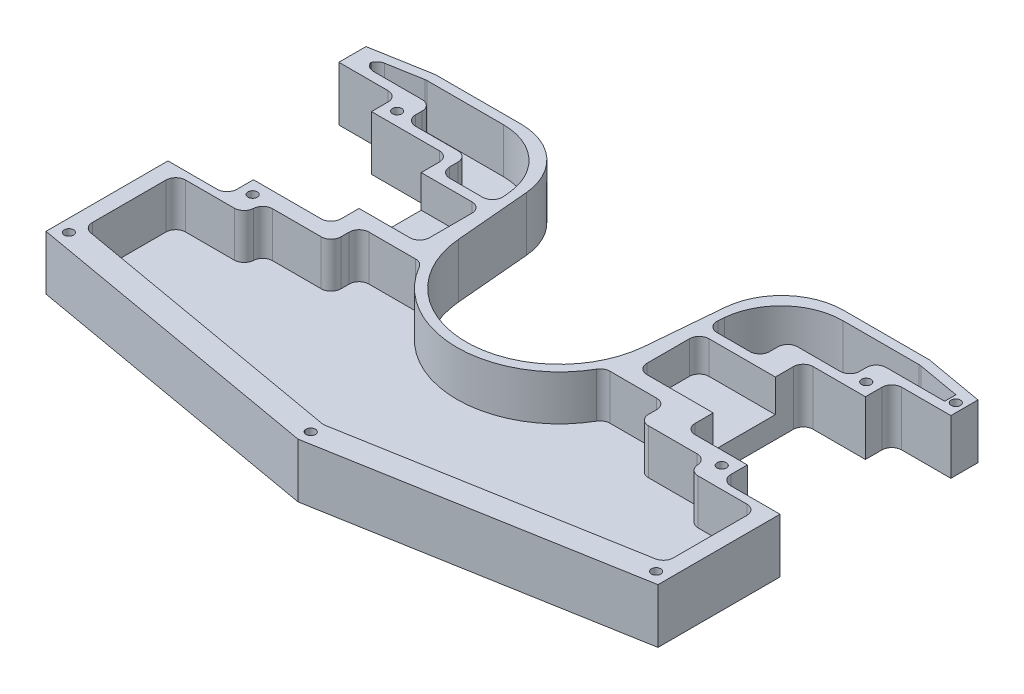
SolidWorks part; units mm, degrees
material "Nailon 101"
ref_plane "Alzado" through (0, 0, 0) normal (0, 0, 1) x (1, 0, 0)
ref_plane "Planta" through (0, 0, 0) normal (0, 1, 0) x (1, 0, 0)
ref_plane "Vista lateral" through (0, 0, 0) normal (1, 0, 0) x (0, 0, -1)
sketch "Croquis2" plane through (0, 0, 0) normal (0, 1, 0) x (1, 0, 0)
  line L0 (0, 0) -> (0, 115) construction
  line L1 (108.5, -65) -> (-108.5, -65) construction
  line L2 (108.5, -65) -> (108.5, 35) construction
  line L3 (108.5, 35) -> (-108.5, 35) construction
  line L4 (-108.5, -65) -> (-108.5, 35) construction
  line L5 (-55.9619, 30) -> (37.6455, 30) construction
  line L6 (-55.9619, 25) -> (37.6455, 25) construction
  line L7 (0, 0) -> (0, -84.14) construction
  line L8 (-98.5, -66.7718) -> (0, -84.14)
  line L9 (0, -84.14) -> (98.5, -66.7718)
  line L10 (-79.5, 39.59) -> (-19.0451, 147.5) construction
  line L11 (-19.0451, 147.5) -> (19.0451, 147.5) construction
  line L12 (19.0451, 147.5) -> (79.5, 39.59) construction
  line L13 (0, 115) -> (0, 147.5) construction
  line L14 (-98.5, 36.2398) -> (-79.5, 39.59)
  line L15 (98.5, 36.2398) -> (79.5, 39.59)
  line L16 (-79.5, 39.59) -> (-33.5783, 39.59)
  line L17 (-37.5, 0) -> (37.5, 0) construction
  line L18 (-77.5, 10) -> (-37.5, 10) construction
  line L19 (-77.5, 10) -> (-77.5, -10) construction
  line L20 (-77.5, -10) -> (-37.5, -10) construction
  line L21 (-37.5, 10) -> (-37.5, -10) construction
  line L22 (37.5, -10) -> (77.5, -10) construction
  line L23 (37.5, -10) -> (37.5, 10) construction
  line L24 (37.5, 10) -> (77.5, 10) construction
  line L25 (77.5, -10) -> (77.5, 10) construction
  line L26 (-77.5, 0) -> (-108.5, 0) construction
  line L27 (77.5, 0) -> (108.5, 0) construction
  line L28 (79.5, -27.5) -> (79.5, -19)
  line L29 (-79.5, -27.5) -> (-98.5, -27.5)
  line L30 (-79.5, -27.5) -> (-79.5, -19)
  line L31 (-79.5, 27.5) -> (-98.5, 27.5)
  line L32 (-98.5, -27.5) -> (-98.5, 27.5) construction
  line L33 (-79.5, -27.5) -> (-98.5, 27.5) construction
  line L34 (-79.5, 27.5) -> (-98.5, -27.5) construction
  line L35 (79.5, 27.5) -> (98.5, 27.5)
  line L37 (79.5, -27.5) -> (98.5, -27.5)
  line L38 (-37.5, -25) -> (33.9933, -25) construction
  line L39 (-66.8039, -30) -> (8.1961, -30) construction
  line L40 (-66.8039, -30) -> (-66.8039, -65) construction
  line L41 (8.1961, -30) -> (8.1961, -65) construction
  line L42 (-108.5, -65) -> (-117.3163, -15) construction
  line L43 (-117.3163, -15) -> (-108.5, 35) construction
  line L44 (-108.5, -15) -> (-117.3163, -15) construction
  line L45 (108.5, -65) -> (117.3163, -15) construction
  line L46 (117.3163, -15) -> (108.5, 35) construction
  line L47 (108.5, -15) -> (117.3163, -15) construction
  line L48 (-25, 0) -> (-25, 115) construction
  line L49 (25, 0) -> (25, 115) construction
  line L50 (-79.5, 27.5) -> (-79.5, 39.59) construction
  line L51 (-79.5, 39.59) -> (-88.2242, 44.4776) construction
  line L52 (-88.2242, 44.4776) -> (-27.7693, 152.3876) construction
  line L53 (-27.7693, 152.3876) -> (-19.0451, 147.5) construction
  line L54 (27.7693, 152.3876) -> (19.0451, 147.5) construction
  line L55 (88.2242, 44.4776) -> (27.7693, 152.3876) construction
  line L56 (79.5, 39.59) -> (88.2242, 44.4776) construction
  line L57 (-29.8858, -2.6147) -> (-33.5783, 39.59)
  line L58 (29.8858, -2.6147) -> (33.5783, 39.59)
  line L59 (33.5783, 39.59) -> (79.5, 39.59)
  line L60 (-93.5, -59.53) -> (0, -76.0166)
  line L61 (-98.5, -56.609) -> (-98.5, -27.5)
  line L62 (0, -76.0166) -> (93.5, -59.53)
  line L63 (-98.5, -56.609) -> (-98.5, -66.7718)
  line L64 (-98.5, -56.609) -> (-98.5, -27.5)
  line L65 (-98.5, 27.5) -> (-98.5, 36.2398)
  line L66 (98.5, -27.5) -> (98.5, -66.7718)
  line L67 (-37.5, 10) -> (-30.9895, 10)
  line L68 (-93.5, -30) -> (-93.5, -59.53)
  line L69 (93.5, -59.53) -> (93.5, -30)
  line L70 (37.5, 10) -> (30.9895, 10)
  line L71 (98.5, 27.5) -> (98.5, 36.2398)
  line L72 (-54.5, 0) -> (-77.5, 0) construction
  line L73 (-79.5, 19) -> (-54.5, 19) construction
  line L74 (-79.5, 19) -> (-79.5, -19) construction
  line L75 (-79.5, -19) -> (-54.5, -19) construction
  line L76 (-54.5, 19) -> (-54.5, -19) construction
  line L77 (59.5, 0) -> (79.5, 0) construction
  line L78 (79.5, -19) -> (59.5, -19) construction
  line L79 (79.5, -19) -> (79.5, 19) construction
  line L80 (79.5, 19) -> (59.5, 19) construction
  line L81 (59.5, -19) -> (59.5, 19) construction
  line L82 (-93.5, -30) -> (-71.5, -30)
  line L83 (98.5, -66.7718) -> (98.5, -27.5)
  line L84 (-71.5, -30) -> (-71.5, -24)
  line L85 (-71.5, -24) -> (-49.5, -24)
  line L86 (-49.5, -24) -> (-49.5, -15)
  line L87 (-79.5, -19) -> (-54.5, -19)
  line L88 (-54.5, -19) -> (-54.5, -10)
  line L89 (-54.5, -10) -> (-37.5, -10)
  line L90 (-37.5, -10) -> (-37.5, 10) construction
  line L91 (-37.5, 10) -> (-54.5, 10)
  line L92 (-54.5, 10) -> (-54.5, 19)
  line L93 (-54.5, 19) -> (-79.5, 19)
  line L94 (-79.5, 19) -> (-79.5, 27.5)
  line L95 (79.5, -19) -> (59.5, -19)
  line L96 (59.5, -19) -> (59.5, -10)
  line L97 (59.5, -10) -> (37.5, -10)
  line L98 (37.5, -10) -> (37.5, 10) construction
  line L99 (37.5, 10) -> (59.5, 10)
  line L100 (59.5, 10) -> (59.5, 19)
  line L101 (59.5, 19) -> (79.5, 19)
  line L102 (79.5, 19) -> (79.5, 27.5)
  line L103 (-37.5, -10) -> (-28.2843, -10)
  line L104 (-49.5, -15) -> (-29.3939, -15)
  line L105 (49.5, -15) -> (29.3939, -15)
  line L106 (49.5, -24) -> (49.5, -15)
  line L107 (71.5, -24) -> (49.5, -24)
  line L108 (71.5, -30) -> (71.5, -24)
  line L109 (93.5, -30) -> (71.5, -30)
  line L110 (37.5, -10) -> (28.2843, -10)
  line L111 (-54.5, 19) -> (-54.5, 39.59)
  line L112 (-39.0577, -35.2251) -> (35.9399, -35.8207) construction
  line L113 (-39.0577, -35.2251) -> (-39.3357, -70.224) construction
  line L114 (-39.3357, -70.224) -> (35.662, -70.8196) construction
  line L115 (35.9399, -35.8207) -> (35.662, -70.8196) construction
  line L116 (-93.5, 30.5) -> (-71.5, 30.5)
  line L117 (-71.5, 30.5) -> (-71.5, 22)
  line L118 (-71.5, 22) -> (-57.5, 22)
  line L119 (-57.5, 22) -> (-57.5, 36.59) construction
  line L120 (-57.5, 36.59) -> (-79.5, 36.59)
  line L121 (-79.5, 36.59) -> (-93.5, 34.1214)
  line L122 (-93.5, 34.1214) -> (-93.5, 30.5)
  line L123 (79.5, 36.59) -> (93.5, 34.1214)
  line L124 (57.5, 36.59) -> (79.5, 36.59)
  line L125 (57.5, 22) -> (57.5, 36.59) construction
  line L126 (71.5, 22) -> (57.5, 22)
  line L127 (71.5, 30.5) -> (71.5, 22)
  line L128 (93.5, 30.5) -> (71.5, 30.5)
  line L129 (93.5, 34.1214) -> (93.5, 30.5)
  line L130 (59.5, 19) -> (59.5, 39.59)
  line L131 (-57.5, 22) -> (-51.5, 22)
  line L132 (-51.5, 22) -> (-51.5, 13)
  line L133 (-51.5, 13) -> (-34.2634, 13)
  line L134 (-34.2634, 13) -> (-36.3273, 36.59)
  line L135 (-36.3273, 36.59) -> (-57.5, 36.59)
  line L136 (57.5, 22) -> (51.5, 22)
  line L137 (51.5, 22) -> (51.5, 13)
  line L138 (51.5, 13) -> (34.2634, 13)
  line L139 (34.2634, 13) -> (36.3273, 36.59)
  line L140 (36.3273, 36.59) -> (57.5, 36.59)
  line L141 (-54.5, -10) -> (-54.5, 10)
  line L142 (79.5, -19) -> (79.5, 19)
  line L143 (59.5, -10) -> (59.5, 10)
  line L144 (-35, -10) -> (-35, 10)
  line L145 (35, -10) -> (35, 10)
  circle A0 centre (0, 115) radius 2.5 construction
  circle A1 centre (0, 115) radius 85 construction
  circle A2 centre (0, 115) radius 32.5 construction
  circle A3 centre (0, 115) radius 25 construction
  circle A4 centre (0, 0) radius 25 construction
  circle A5 centre (0, 0) radius 18 construction
  arc A6 (-29.8858, -2.6147) -> (29.8858, -2.6147) centre (0, 0) ccw
  arc A7 (-29.3939, -15) -> (29.3939, -15) centre (0, 0) ccw
  point P0 (0, 0)
  point P9 (0, -65)
  point P39 (-89, 0)
  point P58 (0, 0)
  dimension "D1" = 5
  dimension "D2" = 170
  dimension "D5" = 65
  dimension "D6" = 50
  dimension "D8" = 50
  dimension "D9" = 36
  dimension "D25" = 10
  dimension "D28" = 3
  dimension "D40" = 5
  dimension "D3" = 10
  dimension "D4" = 10
  dimension "D7" = 5
  dimension "D10" = 40
  dimension "D11" = 20
  dimension "D12" = 19
  dimension "D13" = 10
  dimension "D14" = 35
  dimension "D15" = 75
  dimension "D16" = 2
  dimension "D17" = 5
  dimension "D18" = 10
  dimension "D19" = 10
  dimension "D20" = 55
  dimension "D21" = 75
  dimension "D22" = 100
  dimension "D23" = 10
  dimension "D24" = 12.09
  dimension "D26" = 8
  dimension "D27" = 5
  dimension "D29" = 84.14
  dimension "D30" = 25
  dimension "D31" = 38
  dimension "D32" = 38
  dimension "D33" = 20
  dimension "D34" = 8
  dimension "D35" = 5
  dimension "D36" = 5
  dimension "D37" = 5
  dimension "D38" = 75
  dimension "D39" = 35
  dimension "D41" = 5
  dimension "D42" = 3
  dimension "D43" = 3
  dimension "D44" = 3
  dimension "D45" = 8
  dimension "D46" = 3
  dimension "D47" = 3
  dimension "D48" = 3
  dimension "D49" = 3
  dimension "D50" = 2.5
extrude "Saliente-Extruir1" add sketch "Croquis2" along normal blind 3 contours A7 L104 L86 L85 L84 L82 L68 L60 L62 L69 L109 L108 L107 L106 L105 | A6 L103 L89 L88 L87 L30 L29 L61 L63 L8 L9 L66 L37 L28 L95 L96 L97 L110 L104 A7 L105 L106 L107 L108 L109 L69 L62 L60 L68 L82 L84 L85 L86 | A6 L57 L67 L91 L141 L89 L103 | L135 L134 L133 L132 L131 L111 L92 L91 L67 L57 L16 | L134 L135 L111 L131 L132 L133 | L111 L135 L120 L121 L122 L116 L117 L118 L131 | L135 L111 L16 L14 L65 L31 L94 L93 L131 L118 L117 L116 L122 L121 L120 | A6 L110 L97 L143 L99 L70 L58 | L139 L140 L130 L59 L58 L70 L99 L100 L136 L137 L138 | L140 L139 L138 L137 L136 L130 | L130 L140 L124 L123 L129 L128 L127 L126 L136 L101 L102 L35 L71 L15 L59 | L140 L130 L136 L126 L127 L128 L129 L123 L124 | A6 L57 L67 L144 L103 | A6 L110 L145 L70 L58 region at (-96.3951, 0, 61.6904) region at (79.096, 0, -30.0077) region at (-44.75, 0, 0) region at (47.25, 0, 0) region at (59.0891, 0, -14.5) region at (-54.1221, 0, -14.5) region at (71.9242, 0, -30.8632) region at (46.2202, 0, -25.6558) region at (-32.4518, 0, 0.7728) region at (-77.1906, 0, -29.9463) region at (32.4518, 0, 0.7728) region at (-68.9392, 0, -30.5496) region at (-44.3744, 0, -25.0327) region at (0, 0, 46.0536)
extrude "Saliente-Extruir2" add sketch "Croquis2<3>" along normal blind 17.5 contours A6 L103 L89 L88 L87 L30 L29 L61 L63 L8 L9 L66 L37 L28 L95 L96 L97 L110 L104 A7 L105 L106 L107 L108 L109 L69 L62 L60 L68 L82 L84 L85 L86 | L135 L134 L133 L132 L131 L111 L92 L91 L67 L57 L16 | L135 L111 L16 L14 L65 L31 L94 L93 L131 L118 L117 L116 L122 L121 L120 | L139 L140 L130 L59 L58 L70 L99 L100 L136 L137 L138 | L130 L140 L124 L123 L129 L128 L127 L126 L136 L101 L102 L35 L71 L15 L59 | A6 L57 L67 L144 L103 | A6 L110 L145 L70 L58 region at (-96.3951, 0, 61.6904) region at (79.096, 0, -30.0077) region at (59.0891, 0, -14.5) region at (-54.1221, 0, -14.5) region at (-32.4518, 0, 0.7728) region at (-77.1906, 0, -29.9463) region at (32.4518, 0, 0.7728)
sketch "Croquis2<3>" plane through (0, 0, 0) normal (0, 1, 0) x (1, 0, 0) same geometry as "Croquis2"
fillet "Redondeo1" radius 3.175 5 edges at (-79.5, 10.25, -36.59) (-51.5, 10.25, -13) (-71.5, 10.25, -22) (-93.5, 10.25, -30.5) (-93.5, 10.25, -34.1214)
fillet "Redondeo2" [suppressed] radius 3.175
fillet "Redondeo3" radius 3.175 11 edges at (-93.5, 10.25, 59.53) (0, 10.25, 76.0166) (93.5, 10.25, 59.53) (93.5, 10.25, 30) (71.5, 10.25, 24) (49.5, 10.25, 15) (29.3939, 10.25, 15) (-29.3939, 10.25, 15) (-49.5, 10.25, 15) (-71.5, 10.25, 24) (-93.5, 10.25, 30)
fillet "Redondeo5" radius 3.175 8 edges at (-49.5, 10.25, 24) (-71.5, 10.25, 30) (71.5, 10.25, 30) (49.5, 10.25, 24) (71.5, 10.25, -30.5) (51.5, 10.25, -22) (-51.5, 10.25, -22) (-71.5, 10.25, -30.5)
sketch "Croquis5" plane through (0, 17.5, 0) normal (0, 1, 0) x (1, 0, 0)
  line L0 (0, -84.14) -> (0, -75.9676) construction
  line L1 (0, -80.0538) -> (-98.5, -62.6856) construction
  line L2 (-98.5, -66.7718) -> (-98.5, -27.5) construction
  line L3 (-98.5, -66.7718) -> (0, -84.14) construction
  line L4 (-79.5, -23.25) -> (-50.6256, -23.25) construction
  line L5 (-79.5, -27.5) -> (-79.5, -19) construction
  line L6 (0, 0) -> (0, -75.9676) construction
  line L7 (0, 0) -> (-54.5, 0) construction
  line L8 (-54.5, -10) -> (-54.5, 10) construction
  line L13 (98.5, 31.8699) -> (92.9369, 31.8699) construction
  line L14 (79.5, -23.25) -> (50.6256, -23.25) construction
  arc A0 (-0.5513, -75.9193) -> (0.5513, -75.9193) centre (0, -72.7926) ccw construction
  circle A1 centre (0, -80.0538) radius 1.5
  circle A2 centre (-94.5, -63.3909) radius 1.5
  arc A3 (-52.675, -24) -> (-49.5, -20.825) centre (-52.675, -20.825) ccw construction
  circle A4 centre (-75.5, -23.25) radius 1.5
  circle A7 centre (-75.5, 23.25) radius 1.5
  circle A8 centre (75.5, 23.25) radius 1.5
  circle A9 centre (95.7185, 31.8699) radius 1.5
  circle A10 centre (75.5, -23.25) radius 1.5
  circle A11 centre (94.5, -63.3909) radius 1.5
  dimension "D1" = 3
  dimension "D2" = 4
  dimension "D3" = 4
extrude "Cortar-Extruir1" cut sketch "Croquis5" against normal blind 10
extrude "Saliente-Extruir3" add sketch "Croquis2<4>" along normal blind 7 contours L103 L144 L67 L91 L141 L89 | L145 L110 L97 L143 L99 L70 region at (-44.75, 0, 0) region at (47.25, 0, 0)
sketch "Croquis2<4>" plane through (0, 0, 0) normal (0, 1, 0) x (1, 0, 0) same geometry as "Croquis2"
fillet "Redondeo6" radius 3.175 12 edges at (79.5, 8.75, -27.5) (79.5, 8.75, 27.5) (59.5, 8.75, 19) (59.5, 8.75, -19) (35, 12.25, -10) (35, 12.25, 10) (-35, 12.25, -10) (-35, 12.25, 10) (-54.5, 8.75, 19) (-54.5, 8.75, -19) (-79.5, 8.75, 27.5) (-79.5, 8.75, -27.5)
fillet "Redondeo7" radius 3.175 1 edges at (-34.2634, 10.25, -13)
fillet "Redondeo8" radius 3.175 4 edges at (79.5, 10.25, -36.59) (71.5, 10.25, -22) (51.5, 10.25, -13) (34.2634, 10.25, -13)
fillet "Redondeo12" radius 20 2 edges at (36.3273, 10.25, -36.59) (-36.3273, 10.25, -36.59)
fillet "Redondeo11" radius 20 2 edges at (33.5783, 8.75, -39.59) (-33.5783, 8.75, -39.59)
